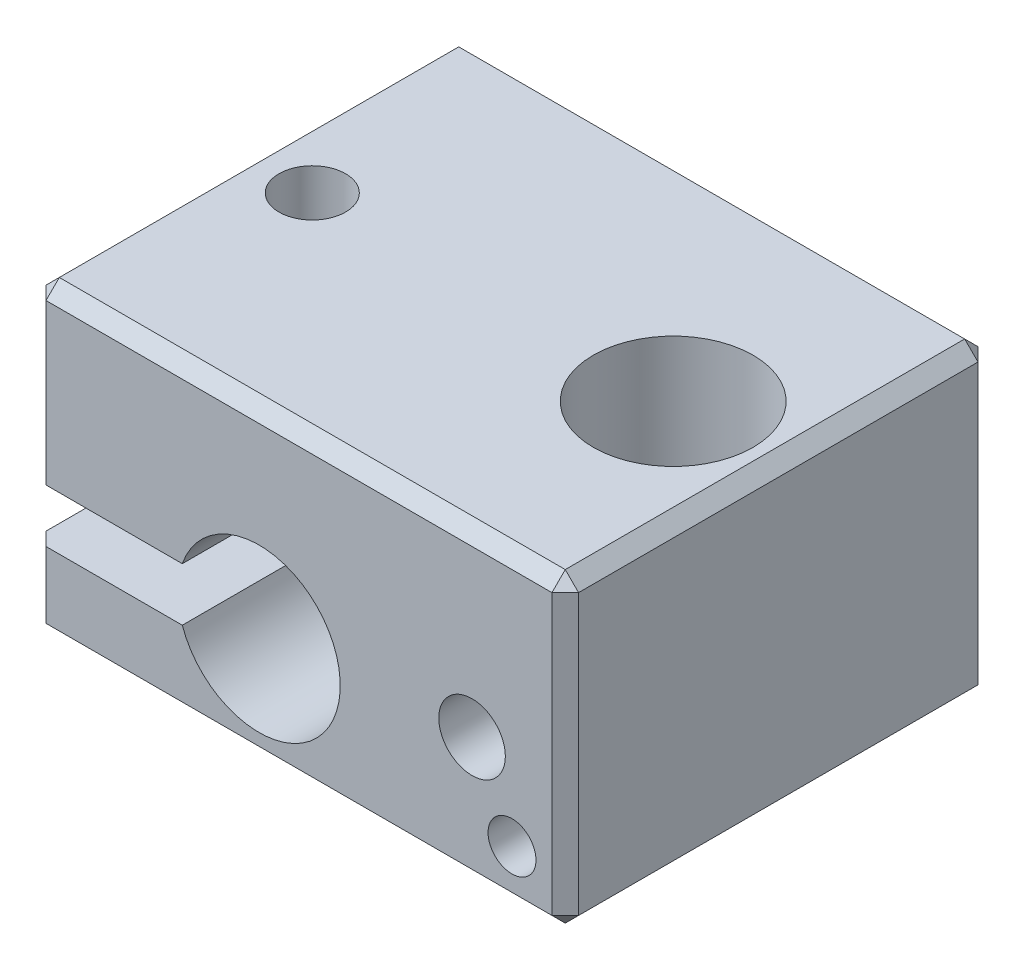
SolidWorks part; units mm, degrees
material "AISI 304"
ref_plane "Front Plane" through (0, 0, 0) normal (0, 0, 1) x (1, 0, 0)
ref_plane "Top Plane" through (0, 0, 0) normal (0, 1, 0) x (1, 0, 0)
ref_plane "Right Plane" through (0, 0, 0) normal (1, 0, 0) x (0, 0, -1)
sketch "Sketch1" plane through (0, 0, 0) normal (0, 0, 1) x (1, 0, 0)
  line L0 (-10, -0.75) -> (-4.3814, -0.75)
  line L1 (-10, -5.75) -> (10, -5.75)
  line L2 (-10, -5.75) -> (-10, 5.75) construction
  line L3 (-10, 5.75) -> (10, 5.75)
  line L4 (10, -5.75) -> (10, 5.75)
  line L5 (-10, -5.75) -> (10, 5.75) construction
  line L6 (-10, 5.75) -> (10, -5.75) construction
  line L7 (-4.3814, -2.75) -> (-10, -2.75)
  line L8 (-10, 5.75) -> (-10, -0.75)
  line L9 (-10, -2.75) -> (-10, -5.75)
  arc A0 (-4.3814, -0.75) -> (-4.3814, -2.75) centre (-1.5, -1.75) cw
  point P0 (0, 0)
  dimension "D3" = 4
  dimension "D5" = 3.05
  dimension "D1" = 20
  dimension "D2" = 11.5
  dimension "D4" = 2
  dimension "D6" = 11.5
extrude "Boss-Extrude1" add sketch "Sketch1" along normal mid plane 16
chamfer "Chamfer1" distance 0.5 angle 45 14 edges at (0, -5.75, -8) (-10, -4.25, -8) (-10, -5.75, 0) (-10, 2.5, -8) (-10, -4.25, 8) (0, -5.75, 8) (-10, 2.5, 8) (10, -5.75, 0) (10, 0, -8) (10, 0, 8) (10, 5.75, 0) (0, 5.75, -8) (0, 5.75, 8) (-10, 5.75, 0)
hole_wizard "M3x0.5 Tapped Hole1" positions "Sketch3" profile "Sketch2" tap size "M3x0.5" standard "ANSI Metric"
sketch "Sketch3" plane through (0, 0, 8) normal (0, 0, 1) x (1, 0, 0)
  line L0 (9.5, -5.75) -> (-9.5, -5.75) construction
  line L1 (10, 5.25) -> (10, -5.25) construction
  point P0 (6.5, -0.95)
  dimension "D1" = 4.8
  dimension "D2" = 3.5
sketch "Sketch2" plane through (6.5, -0.95, 8) normal (1, 0, 0) x (0, -1, 0)
  line L0 (0, 0) -> (0, 4.2511)
  line L1 (0, 4.2511) -> (1.25, 3.5)
  line L2 (1.25, 3.5) -> (1.25, 0)
  line L5 (1.25, 0) -> (0, 0)
  line L10 (0, 4.2511) -> (-1.25, 3.5) construction
  line L11 (0, -6.35) -> (0, 107.95) construction
  dimension "Tap Drill Dia." = 2.5
  dimension "Tap Drill Depth" = 3.5
  dimension "Drill Angle" = 118
cosmetic thread "Hole Thread2" parameters "D1"=3.5, "D2"=3
hole_wizard "Ø1.8 (1.8) Diameter Hole1" positions "Sketch5" profile "Sketch4" hole size "Ø1.8" standard "ANSI Metric"
sketch "Sketch5" plane through (0, 0, 8) normal (0, 0, 1) x (1, 0, 0)
  line L0 (9.5, -5.75) -> (-9.5, -5.75) construction
  line L1 (10, 5.25) -> (10, -5.25) construction
  point P0 (8, -3.75)
  dimension "D1" = 2
  dimension "D2" = 2
sketch "Sketch4" plane through (8, -3.75, 8) normal (1, 0, 0) x (0, -1, 0)
  line L0 (0, 0) -> (0, 2.5408)
  line L1 (0, 2.5408) -> (0.9, 2)
  line L2 (0.9, 2) -> (0.9, 0)
  line L5 (0.9, 0) -> (0, 0)
  line L10 (0, 2.5408) -> (-0.9, 2) construction
  line L11 (0, -6.35) -> (0, 107.95) construction
  dimension "Hole Dia." = 1.8
  dimension "Hole Depth" = 2
  dimension "Drill Angle" = 118
hole_wizard "Ø1.6 (1.6) Diameter Hole1" positions "Sketch7" profile "Sketch6" hole size "Ø1.6" standard "ANSI Metric"
sketch "Sketch7" plane through (0, 0, 8) normal (0, 0, 1) x (1, 0, 0)
  point P0 (8, -3.75)
sketch "Sketch6" plane through (8, -3.75, 8) normal (1, 0, 0) x (0, -1, 0)
  line L0 (0, 0) -> (0, 4.9807)
  line L1 (0, 4.9807) -> (0.8, 4.5)
  line L2 (0.8, 4.5) -> (0.8, 0)
  line L5 (0.8, 0) -> (0, 0)
  line L10 (0, 4.9807) -> (-0.8, 4.5) construction
  line L11 (0, -6.35) -> (0, 107.95) construction
  dimension "Hole Dia." = 1.6
  dimension "Hole Depth" = 4.5
  dimension "Drill Angle" = 118
hole_wizard "M3x0.5 Tapped Hole2" positions "Sketch9" profile "Sketch8" tap size "M3x0.5" standard "ANSI Metric" end condition through all
sketch "Sketch9" plane through (0, 5.75, 0) normal (0, 1, 0) x (1, 0, 0)
  line L0 (10, 7.5) -> (10, -7.5) construction
  point P0 (-7.5, 0)
  dimension "D1" = 17.5
sketch "Sketch8" plane through (-7.5, 5.75, 0) normal (1, 0, 0) x (0, 0, 1)
  line L0 (0, 0) -> (0, 11.5)
  line L1 (0, 11.5) -> (1.25, 11.5)
  line L2 (1.25, 11.5) -> (1.25, 0)
  line L5 (1.25, 0) -> (0, 0)
  line L11 (0, -6.35) -> (0, 107.95) construction
  dimension "Thread Major Dia." = 2.5
  dimension "Thru Tap Drill Depth" = 11.5
hole_wizard "M6x1.0 Tapped Hole1" positions "Sketch11" profile "Sketch12" tap size "M6x1.0" standard "ANSI Metric" end condition through all
sketch "Sketch11" plane through (0, 5.75, 0) normal (0, 1, 0) x (1, 0, 0)
  point P0 (6.0538, 0)
sketch "Sketch12" plane through (6.0538, 5.75, 0) normal (1, 0, 0) x (0, 0, 1)
  line L0 (0, 0) -> (0, 11.5)
  line L1 (0, 11.5) -> (3, 11.5)
  line L2 (3, 11.5) -> (3, 0)
  line L5 (3, 0) -> (0, 0)
  line L11 (0, -6.35) -> (0, 107.95) construction
  dimension "Thread Major Dia." = 6
  dimension "Thru Tap Drill Depth" = 11.5
